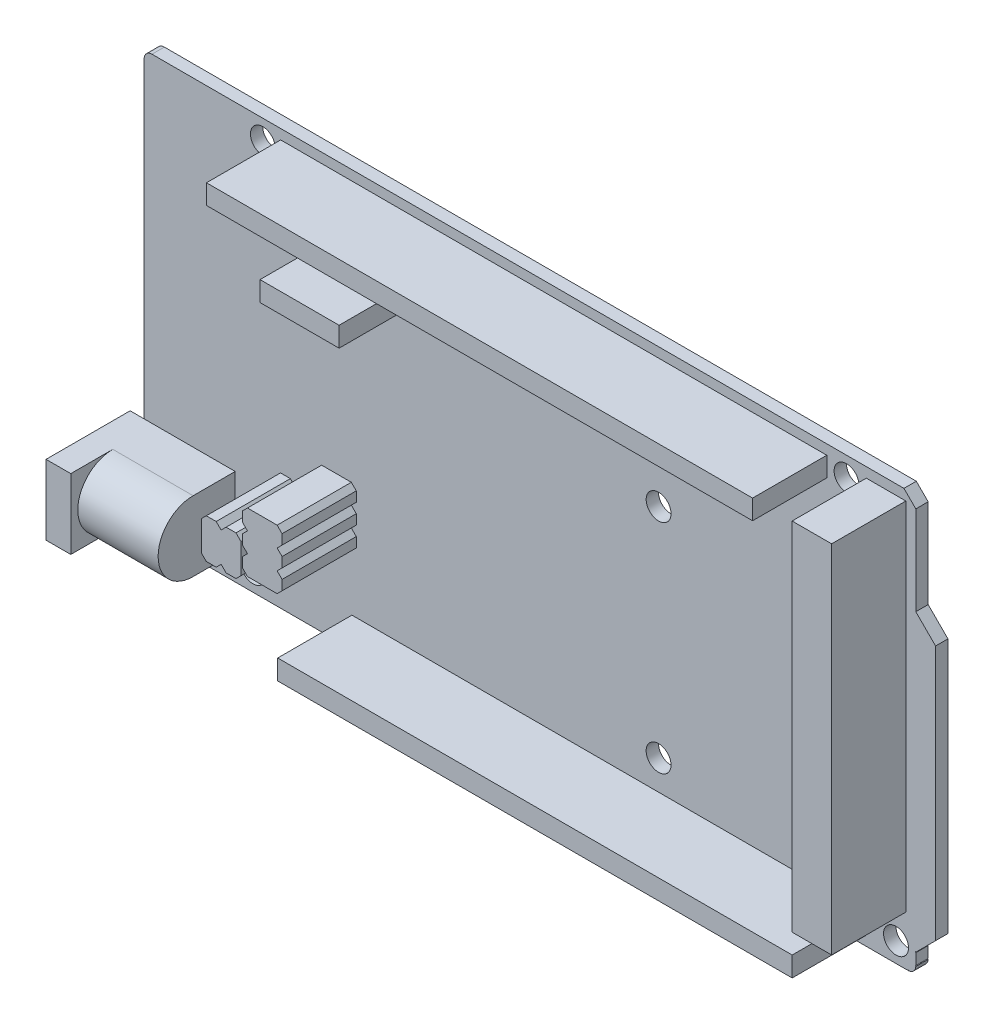
SolidWorks part; units mm, degrees
ref_plane "Front Plane" through (0, 0, 0) normal (0, 0, 1) x (1, 0, 0)
ref_plane "Top Plane" through (0, 0, 0) normal (0, 1, 0) x (1, 0, 0)
ref_plane "Right Plane" through (0, 0, 0) normal (1, 0, 0) x (0, 0, -1)
sketch "20" plane through (0, 0, 0) normal (0, 0, 1) x (1, 0, 0)
  line L0 (97.536, 53.34) -> (99.06, 51.816)
  line L1 (99.06, 40.386) -> (101.6, 37.846)
  line L2 (101.6, 37.846) -> (101.6, 5.08)
  line L3 (101.6, 5.08) -> (99.06, 2.54)
  line L4 (99.06, 2.54) -> (99.06, 1)
  line L5 (98.06, 0) -> (1, 0)
  line L6 (0, 1) -> (0, 52.34)
  line L7 (1, 53.34) -> (97.536, 53.34)
  line L8 (99.06, 51.816) -> (99.06, 40.386)
  circle A0 centre (96.52, 2.54) radius 1.6
  circle A1 centre (15.24, 50.8) radius 1.6
  circle A2 centre (90.17, 50.8) radius 1.6
  circle A3 centre (13.97, 2.54) radius 1.6
  circle A4 centre (66.04, 35.56) radius 1.6
  circle A5 centre (66.04, 7.62) radius 1.6
  arc A18 (101.5365, 5.08) -> (101.5551, 5.1249) centre (101.6, 5.08) ccw
  arc A19 (99.1235, 2.54) -> (99.1049, 2.4951) centre (99.06, 2.54) ccw
  arc A22 (98.9965, 1) -> (99.1235, 1) centre (99.06, 1) ccw
  arc A24 (98.06, 0) -> (99.06, 1) centre (98.06, 1) ccw
  arc A25 (98.06, 0.0635) -> (98.06, -0.0635) centre (98.06, 0) ccw
  arc A26 (99.1235, 1) -> (98.9965, 1) centre (99.06, 1) ccw
  arc A28 (98.06, -0.0635) -> (98.06, 0.0635) centre (98.06, 0) ccw
  arc A29 (0, 1) -> (1, 0) centre (1, 1) ccw
  arc A34 (1, 53.34) -> (0, 52.34) centre (1, 52.34) ccw
sketch "21" plane through (0, 0, 0) normal (0, 0, 1) x (1, 0, 0)
  line L0 (11.3665, 3.302) -> (5.969, 3.302)
  line L1 (11.684, 5.5245) -> (11.684, 10.922)
  line L3 (17.5213, 52.07) -> (87.6306, 52.07)
  line L4 (17.5213, 52.07) -> (17.5213, 49.5465)
  line L5 (17.5213, 49.5465) -> (87.6306, 49.5465)
  line L6 (92.7042, 6.3442) -> (97.7781, 6.3442)
  line L7 (92.7042, 6.3442) -> (92.7042, 52.0567)
  line L8 (92.7042, 52.0567) -> (97.7781, 52.0567)
  line L9 (26.67, 3.81) -> (92.7147, 3.81)
  line L10 (26.67, 3.81) -> (26.67, 1.2534)
  line L11 (26.67, 1.2534) -> (92.7147, 1.2534)
  line L12 (92.7147, 3.81) -> (92.7147, 1.2534)
  line L13 (97.7781, 6.3442) -> (97.7781, 52.0567)
  line L14 (87.6306, 52.07) -> (87.6306, 49.5465)
  line L15 (24.397, 44.7418) -> (34.5473, 44.7418)
  line L16 (24.397, 44.7418) -> (24.397, 42.1903)
  line L17 (24.397, 42.1903) -> (34.5473, 42.1903)
  line L18 (34.5473, 44.7418) -> (34.5473, 42.1903)
  line L1284 (26.5938, 10.922) -> (27.2288, 11.557)
  line L1285 (27.2288, 12.827) -> (26.5938, 13.462)
  line L1286 (26.5938, 13.462) -> (27.2288, 14.097)
  line L1287 (27.2288, 15.367) -> (26.5938, 16.002)
  line L1288 (26.5938, 10.922) -> (22.7838, 10.922)
  line L1289 (22.7838, 10.922) -> (22.1488, 11.557)
  line L1290 (22.1488, 11.557) -> (22.1488, 12.827)
  line L1291 (22.1488, 12.827) -> (22.7838, 13.462)
  line L1292 (22.7838, 13.462) -> (22.1488, 14.097)
  line L1293 (22.1488, 14.097) -> (22.1488, 15.367)
  line L1294 (22.1488, 15.367) -> (22.7838, 16.002)
  line L1297 (27.2288, 14.097) -> (27.2288, 15.367)
  line L1298 (27.2288, 11.557) -> (27.2288, 12.827)
  line L1299 (26.5938, 16.002) -> (27.2288, 16.637)
  line L1300 (27.2288, 17.907) -> (26.5938, 18.542)
  line L1301 (22.7838, 16.002) -> (22.1488, 16.637)
  line L1302 (22.1488, 16.637) -> (22.1488, 17.907)
  line L1303 (22.1488, 17.907) -> (22.7838, 18.542)
  line L1304 (22.7838, 18.542) -> (26.5938, 18.542)
  line L1305 (27.2288, 16.637) -> (27.2288, 17.907)
  line L1312 (4.191, 25.781) -> (4.191, 18.669)
  line L1313 (4.191, 18.669) -> (2.413, 18.669)
  line L1314 (2.413, 18.669) -> (2.413, 17.907)
  line L1315 (2.413, 17.907) -> (0.381, 17.907)
  line L1316 (0.381, 17.907) -> (0.381, 18.669)
  line L1317 (0.381, 18.669) -> (-0.889, 18.669)
  line L1318 (-0.889, 18.669) -> (-0.889, 25.781)
  line L1319 (-0.889, 25.781) -> (0.381, 25.781)
  line L1320 (0.381, 25.781) -> (0.381, 26.543)
  line L1321 (0.381, 26.543) -> (2.413, 26.543)
  line L1322 (2.413, 26.543) -> (2.413, 25.781)
  line L1323 (2.413, 25.781) -> (4.191, 25.781)
  line L1347 (21.9456, 14.4018) -> (21.3106, 15.0368)
  line L1348 (20.0406, 15.0368) -> (19.4056, 14.4018)
  line L1349 (19.4056, 14.4018) -> (18.7706, 15.0368)
  line L1350 (17.5006, 15.0368) -> (16.8656, 14.4018)
  line L1351 (21.9456, 14.4018) -> (21.9456, 10.5918)
  line L1352 (21.9456, 10.5918) -> (21.3106, 9.9568)
  line L1353 (21.3106, 9.9568) -> (20.0406, 9.9568)
  line L1354 (20.0406, 9.9568) -> (19.4056, 10.5918)
  line L1355 (19.4056, 10.5918) -> (18.7706, 9.9568)
  line L1356 (18.7706, 9.9568) -> (17.5006, 9.9568)
  line L1357 (17.5006, 9.9568) -> (16.8656, 10.5918)
  line L1359 (16.8656, 10.5918) -> (16.8656, 14.4018)
  line L1360 (18.7706, 15.0368) -> (17.5006, 15.0368)
  line L1361 (21.3106, 15.0368) -> (20.0406, 15.0368)
  line L1793 (11.684, 5.5245) -> (11.684, 3.302)
  line L1794 (11.684, 3.302) -> (11.3665, 3.302)
  line L1795 (11.684, 10.922) -> (11.684, 12.2936)
  line L1796 (11.684, 12.2936) -> (1.6764, 12.2936)
  line L1797 (1.6764, 12.2936) -> (-1.8034, 12.2936)
  line L1798 (-1.8034, 12.2936) -> (-1.8034, 3.302)
  line L1799 (-1.8034, 3.302) -> (5.969, 3.302)
  arc A3622 (11.7157, 12.2936) -> (11.6522, 12.2936) centre (11.684, 12.2936) ccw
  arc A3625 (11.684, 12.2618) -> (11.684, 12.3254) centre (11.684, 12.2936) ccw
extrude "Boss-Extrude1" add sketch "20" along normal blind 1.5875 contours L7 A34 L6 A29 L5 A25 A28 A24 A22 A26 L4 A19 L3 L2 L1 L8 L0 A0 A1 A2 A3 A4 A5 region at (50.2996, 26.5931, 0)
extrude "Boss-Extrude3" add sketch "21" along normal blind 9.525 from surface separate body contours L6 L13 L8 L7 | L1289 L1290 L1291 L1292 L1293 L1294 L1301 L1302 L1303 L1304 L1300 L1305 L1299 L1287 L1297 L1286 L1285 L1298 L1284 L1288 | L1354 L1355 L1356 L1357 L1359 L1350 L1360 L1349 L1348 L1361 L1347 L1351 L1352 L1353 | L17 L18 L15 L16 | L5 L14 L3 L4 | L9 L12 L11 L10 region at (95.2411, 29.2004, 0) starting at face at (72.8584, 20.1421, 1.5875)
extrude "Boss-Extrude6" add sketch "21<6>" along direction (0, 0, -1) on the side of the normal blind 10.795 from offset 1.5875 separate body contours L1798 L1799 L0 L1794 L1793 L1 L1795 L1796 L1797 region at (4.9403, 7.7978, 0)
sketch "21<6>" plane through (0, 0, 0) normal (0, 0, 1) x (1, 0, 0) same geometry as "21"
sketch "Sketch4" plane through (11.684, 0, 0) normal (1, 0, 0) x (0, 0, -1)
  line L0 (-6.985, 3.302) -> (-21.6942, 3.302)
  line L1 (-12.3825, 3.302) -> (-1.5875, 3.302) construction
  line L2 (-21.6942, 3.302) -> (-21.6942, 12.2936)
  line L3 (-6.985, 12.2936) -> (-21.6942, 12.2936)
  line L4 (-12.3825, 12.2936) -> (-1.5875, 12.2936) construction
  arc A0 (-6.985, 12.2936) -> (-6.985, 3.302) centre (-6.985, 7.7978) ccw
extrude "Cut-Extrude4" cut sketch "Sketch4" against normal offset from surface (10.3124 mm away) 3.175 up to face at (-1.8034, 7.7978, 6.985)
